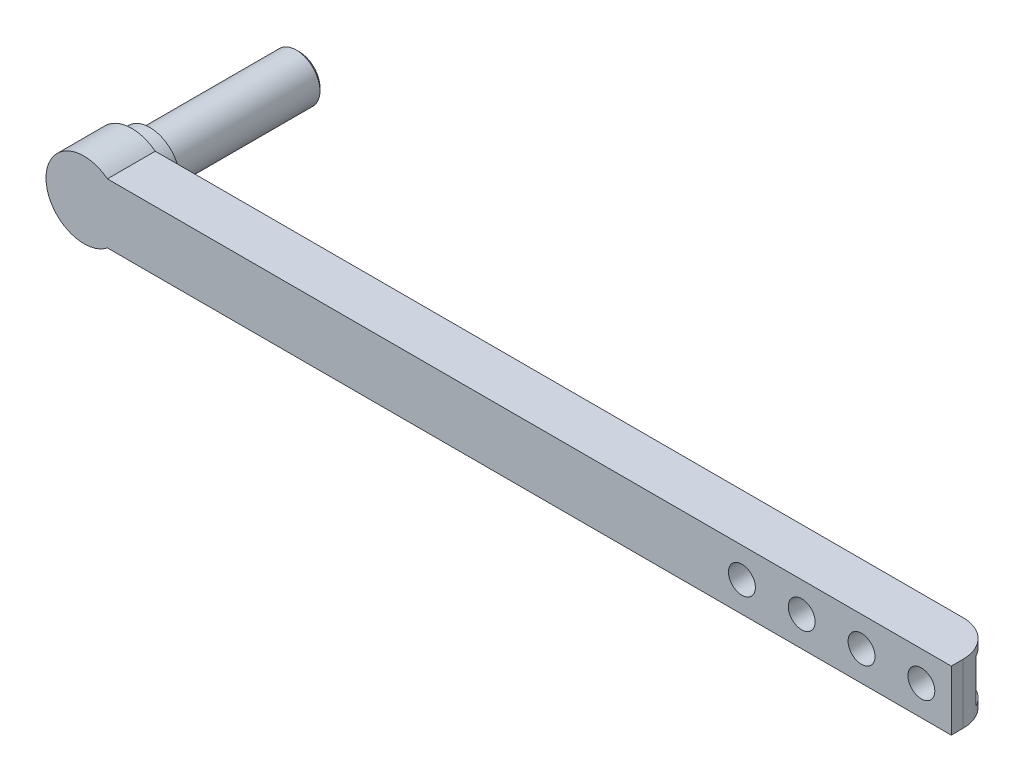
SolidWorks part; units mm, degrees
material "Arm 2 plastic"
ref_plane "Front Plane" through (0, 0, 0) normal (0, 0, 1) x (1, 0, 0)
ref_plane "Top Plane" through (0, 0, 0) normal (0, 1, 0) x (1, 0, 0)
ref_plane "Right Plane" through (0, 0, 0) normal (1, 0, 0) x (0, 0, -1)
sketch "Sketch1" plane through (0, 0, 0) normal (0, 0, 1) x (1, 0, 0)
  circle A0 centre (0, 0) radius 3.95
  dimension "D1" = 7.9
extrude "Boss-Extrude1" add sketch "Sketch1" against normal blind 28
sketch "Sketch2" plane through (0, 0, 0) normal (0, 0, 1) x (1, 0, 0)
  line L0 (0, 0) -> (145, 0) construction
  line L2 (145, 5) -> (0, 5)
  line L3 (145, 5) -> (145, -5)
  line L4 (145, -5) -> (0, -5)
  line L5 (0, 5) -> (0, -5)
  line L6 (72.5, -5) -> (72.5, 5) construction
  line L7 (145, 0) -> (0, 0) construction
  circle A0 centre (0, 0) radius 6.35
  point P275 (72.5, 0)
  circle M7 centre (0, 0) radius 3.95
  dimension "D3" = 12.7
  dimension "D1" = 145
  dimension "D2" = 10
extrude "Boss-Extrude2" add sketch "Sketch2" along normal blind 8 contours L2 A0 L4 L5 M7 | L4 A0 L2 L5 M7 | A0 L4 L3 L2 | L5 M7 | L5 M7 region at (75.3046, 0, 0) region at (5.6022, 2.729, 0) region at (1.9572, 5.1633, 0) region at (1.6764, 0, 0) region at (-1.6764, 0, 0)
sketch "Sketch3" plane through (0, 0, 0) normal (0, 0, 1) x (1, 0, 0)
  circle A0 centre (0, 0) radius 5
  dimension "D1" = 10
extrude "Boss-Extrude3" add sketch "Sketch3" against normal blind 3
sketch "Sketch4" plane through (0, 0, 8) normal (0, 0, 1) x (1, 0, 0)
  line L0 (0, 0) -> (-21.0956, 0) construction
  line L1 (0, 0) -> (10.5478, 18.2693) construction
  line L2 (-6.35, -1.66) -> (-15.3278, -1.66)
  line L3 (-6.35, -1.66) -> (-6.35, 1.66)
  line L4 (-6.35, 1.66) -> (-15.3278, 1.66)
  line L5 (-15.3278, -1.66) -> (-15.3278, 1.66)
  line L6 (-10.8389, 1.66) -> (-10.8389, -1.66) construction
  line L7 (-6.35, 0) -> (-15.3278, 0) construction
  line L8 (1.7374, 6.3292) -> (4.6126, 4.6693)
  line L9 (1.7374, 6.3292) -> (6.2263, 14.1042)
  line L10 (6.2263, 14.1042) -> (9.1015, 12.4443)
  line L11 (4.6126, 4.6693) -> (9.1015, 12.4443)
  line L12 (0, 0) -> (10.5478, -18.2693) construction
  line L13 (4.6126, -4.6693) -> (1.7374, -6.3292)
  line L14 (4.6126, -4.6693) -> (9.1015, -12.4443)
  line L15 (9.1015, -12.4443) -> (6.2263, -14.1042)
  line L16 (1.7374, -6.3292) -> (6.2263, -14.1042)
  arc A0 (3.9144, 5) -> (3.9144, -5) centre (0, 0) ccw construction
  point P4 (-10.8389, 0)
  point P24 (0, 0)
sketch "Sketch5" plane through (145, 0, 0) normal (1, 0, 0) x (0, 0, -1)
  line L0 (0, 5) -> (0, -5) construction
  line L1 (0, 3.625) -> (-3.2, 3.625)
  line L2 (0, 3.625) -> (0, -3.625)
  line L3 (0, -3.625) -> (-3.2, -3.625)
  line L4 (-3.2, 3.625) -> (-3.2, -3.625)
  line L5 (-1.6, -3.625) -> (-1.6, 3.625) construction
  line L6 (0, 0) -> (-3.2, 0) construction
  line L7 (0, 0) -> (-8, 0) construction
  line L8 (-8, 5) -> (-8, -5) construction
  point P264 (-1.6, 0)
  dimension "D1" = 4.8
  dimension "D2" = 7.25
extrude "Cut-Extrude1" cut sketch "Sketch5" against normal blind 42
hole_wizard "M4 Clearance Hole1" positions "Sketch6" profile "Sketch7" hole size "M4" standard "ANSI Metric" end condition through all
sketch "Sketch6" plane through (0, 0, 8) normal (0, 0, 1) x (1, 0, 0)
  line L0 (110, 0) -> (120, 0) construction
  line L1 (120, 0) -> (130, 0) construction
  line L2 (130, 0) -> (140, 0) construction
  line L3 (140, 0) -> (145, 0) construction
  line L4 (145, 5) -> (145, -5) construction
  point P0 (140, 0)
  point P2 (130, 0)
  point P4 (120, 0)
  point P6 (110, 0)
  dimension "D1" = 5
  dimension "D2" = 10
sketch "Sketch7" plane through (140, 0, 8) normal (1, 0, 0) x (0, -1, 0)
  line L0 (0, 0) -> (0, 36)
  line L1 (0, 36) -> (2.25, 36)
  line L2 (2.25, 36) -> (2.25, 0)
  line L5 (2.25, 0) -> (0, 0)
  line L11 (0, -6.35) -> (0, 107.95) construction
  dimension "Thru Hole Dia." = 4.5
  dimension "Thru Hole Depth" = 36
chamfer "Chamfer1" distance 0.5 angle 45 1 edges at (3.95, 0, -28)
fillet "Fillet1" radius 3.7 2 edges at (103, -3.625, 1.6) (103, 3.625, 1.6)
fillet "Fillet5" radius 6 2 edges at (145, -4.3125, 0) (145, 4.3125, 0) tangent propagation no
sketch3d "3DSketch1"
  line L0 (0, 0, 0) -> (0, 0, 8) construction
  line L1 (0, 0, 8) -> (0, 0, 0) construction
  line L3 (0, 0, 4) -> (0, 8.4255, 4) construction
  line L4 (0, 0, 4) -> (7.7639, 0, 4) construction
ref_plane "Plane1" [suppressed] through (5, 0, 0) normal (1, 0, 0) x (0, 0, -1)
split "Split1" [suppressed] bodies to split 106
delete or keep bodies "Body-Delete/Keep 1" [suppressed] type keep bodies bodies 107
